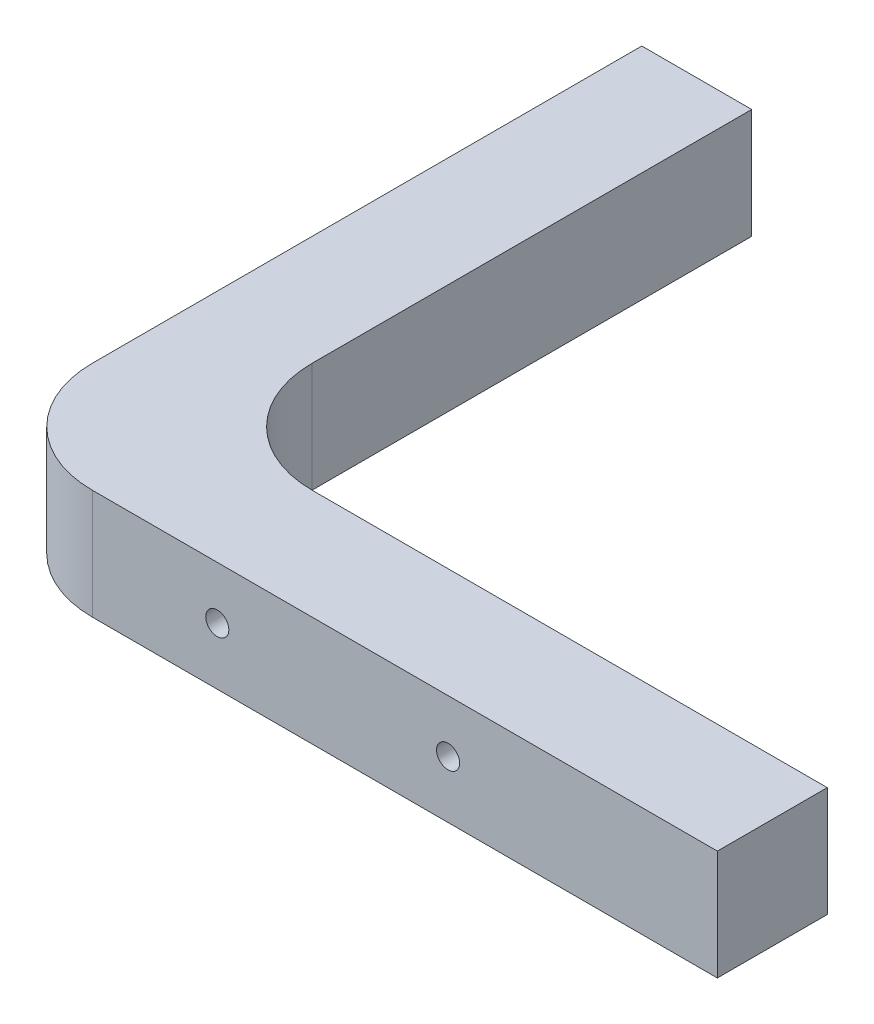
SolidWorks part; units mm, degrees
material "PTFE (general)"
ref_plane "Front Plane" through (0, 0, 0) normal (0, 0, 1) x (1, 0, 0)
ref_plane "Top Plane" through (0, 0, 0) normal (0, 1, 0) x (1, 0, 0)
ref_plane "Right Plane" through (0, 0, 0) normal (1, 0, 0) x (0, 0, -1)
sketch "Sketch1" plane through (0, 0, 0) normal (0, 1, 0) x (1, 0, 0)
  line L0 (23.1763, 46.7218) -> (-90.5737, 46.7218)
  line L1 (-110.5737, 66.7218) -> (-110.5737, 166.7218)
  line L2 (-110.5737, 166.7218) -> (-90.5737, 166.7218)
  line L3 (-90.5737, 166.7218) -> (-90.5737, 86.7218)
  line L4 (-70.5737, 66.7218) -> (23.1763, 66.7218)
  line L5 (23.1763, 66.7218) -> (23.1763, 46.7218)
  arc A0 (-90.5737, 46.7218) -> (-110.5737, 66.7218) centre (-90.5737, 66.7218) cw
  arc A1 (-90.5737, 86.7218) -> (-70.5737, 66.7218) centre (-70.5737, 86.7218) ccw
  point P8 (-110.5737, 46.7218)
  point P11 (-90.5737, 66.7218)
  dimension "D5" = 20
  dimension "D1" = 20
  dimension "D2" = 20
  dimension "D3" = 113.75
  dimension "D4" = 120
extrude "Boss-Extrude1" add sketch "Sketch1" along normal blind 20
sketch "Sketch2" plane through (0, 0, -66.7218) normal (0, 0, -1) x (-1, 0, 0)
  line L0 (-23.1763, 10.3977) -> (70.5737, 10.3977) construction
  line L1 (-23.1763, 20) -> (-23.1763, 0) construction
  line L2 (70.5737, 20) -> (70.5737, 0) construction
  line L3 (46.8237, 20) -> (46.8237, 0) construction
  line L5 (-23.1763, 0) -> (70.5737, 0) construction
  line L6 (-23.1763, 20) -> (70.5737, 20) construction
  circle A0 centre (25.8237, 10.3977) radius 2.1
  circle A2 centre (67.8237, 10.3977) radius 2.1
  dimension "D1" = 4.2
  dimension "D2" = 70
  dimension "D3" = 21
extrude "Cut-Extrude3" cut sketch "Sketch2" against normal up to surface (20 mm away) up to face at (-33.6987, 10, -46.7218)
move or copy body "Body-Move/Copy1" bodies to move or copy 103 copy no translate (0, 0, 46.72) parameters "D1"=0, "D2"=0, "D3"=46.72
move or copy body "Body-Move/Copy2" bodies to move or copy 104 copy no translate (110.57, 0, 0) parameters "D1"=110.57, "D2"=0, "D3"=0
